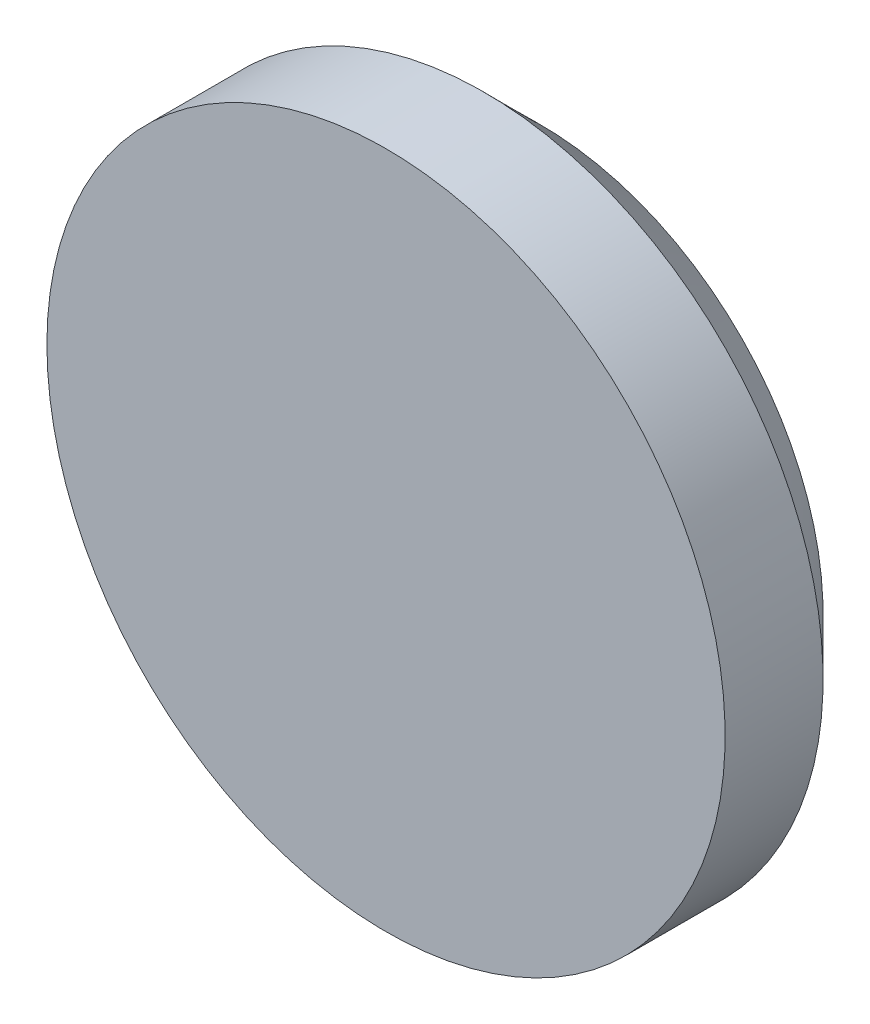
SolidWorks part; units mm, degrees
ref_plane "Front Plane" through (0, 0, 0) normal (0, 0, 1) x (1, 0, 0)
ref_plane "Top Plane" through (0, 0, 0) normal (0, 1, 0) x (1, 0, 0)
ref_plane "Right Plane" through (0, 0, 0) normal (1, 0, 0) x (0, 0, -1)
sketch "Sketch1" plane through (0, 0, 0) normal (0, 1, 0) x (1, 0, 0)
  line L0 (0, 0) -> (0, -1.7318) construction
  line L1 (0, 0) -> (-9, 0)
  line L2 (-9, 0) -> (-9, 2.6)
  line L3 (-9, 2.6) -> (-7.5, 4.1)
  line L4 (-7.5, 4.1) -> (0, 4.1)
  line L5 (0, 4.1) -> (0, 0)
  dimension "D1" = 4.1
  dimension "D2" = 45
  dimension "D3" = 15
  dimension "D4" = 18
revolve "Revolve1" add sketch "Sketch1" angle 360 about L0
equation "\"SensorPadDiameter\"=15"
equation "\"D3@Sketch1\"=\"SensorPadDiameter\""
equation "\"MaxDiameter\"=18"
equation "\"D4@Sketch1\"=\"MaxDiameter\""
